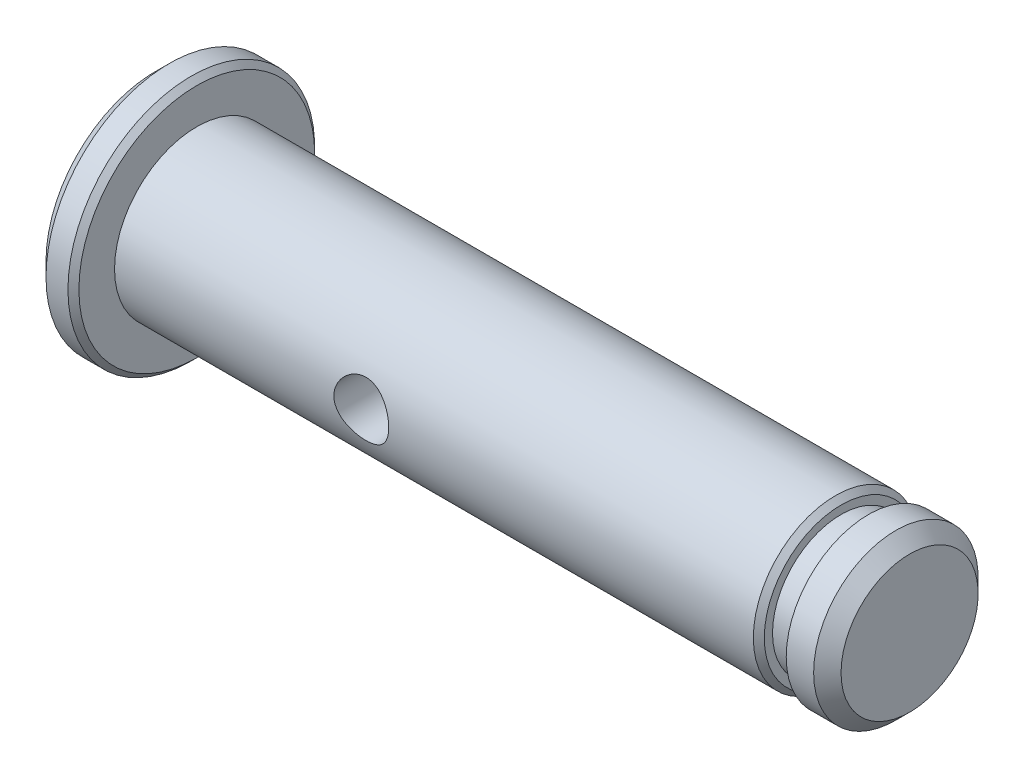
SolidWorks part; units mm, degrees
material "6061-T6 (GB)"
ref_plane "前视" through (0, 0, 0) normal (0, 0, 1) x (1, 0, 0)
ref_plane "上视" through (0, 0, 0) normal (0, 1, 0) x (1, 0, 0)
ref_plane "右视" through (0, 0, 0) normal (1, 0, 0) x (0, 0, -1)
sketch "草图1" plane through (0, 0, 0) normal (0, 0, 1) x (1, 0, 0)
  line L0 (0, 0) -> (77.1831, 0) construction
  line L1 (0, 0) -> (0, 4.5)
  line L2 (0, 4.5) -> (1.5, 4.5)
  line L3 (1.5, 4.5) -> (1.5, 3)
  line L4 (1.5, 3) -> (25, 3)
  line L5 (25, 3) -> (25, 2.5)
  line L6 (25, 2.5) -> (26, 2.5)
  line L7 (26, 2.5) -> (26, 3)
  line L8 (26, 3) -> (27.5, 3)
  line L9 (27.5, 3) -> (27.5, 0)
  line L10 (27.5, 0) -> (0, 0)
  dimension "D1" = 1.5
  dimension "D2" = 1
  dimension "D3" = 0.5
  dimension "D4" = 6
  dimension "D5" = 1.5
  dimension "D6" = 9
  dimension "D7" = 23.5
revolve "旋转1" add sketch "草图1" angle 360 about L0
chamfer "倒角1" distance 0.5 angle 45 2 edges at (27.5, 0, 3) (0, 0, 4.5)
sketch "草图2" plane through (0, 0, 0) normal (0, 0, 1) x (1, 0, 0)
  line L0 (0, 0) -> (26.5863, 0) construction
  line L1 (1.5, -4.5) -> (1.5, 4.5) construction
  circle A0 centre (10.5, 0) radius 1
  dimension "D1" = 2
  dimension "D2" = 9
extrude "切除-拉伸1" cut sketch "草图2" against normal mid plane 30
chamfer "倒角2" distance 0.2 angle 45 2 edges at (25, 0, 3) (1.5, 0, 4.5)
